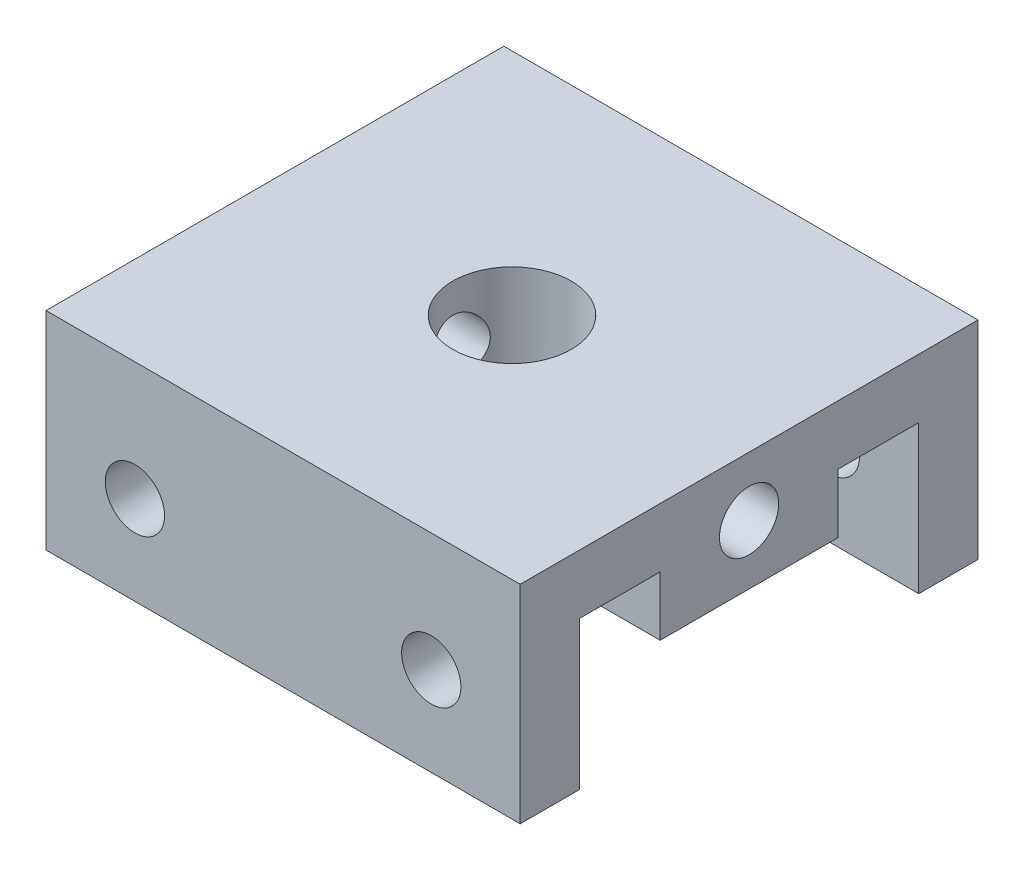
SolidWorks part; units mm, degrees
material "6061-T6 (SS)"
ref_plane "Front Plane" through (0, 0, 0) normal (0, 0, 1) x (1, 0, 0)
ref_plane "Top Plane" through (0, 0, 0) normal (0, 1, 0) x (1, 0, 0)
ref_plane "Right Plane" through (0, 0, 0) normal (1, 0, 0) x (0, 0, -1)
sketch "Sketch1" plane through (0, 0, 0) normal (1, 0, 0) x (0, 0, -1)
  line L0 (18.175, -22.225) -> (24.525, -22.225)
  line L1 (-24.525, 0) -> (24.525, 0)
  line L2 (-24.525, 0) -> (-24.525, -22.225)
  line L3 (-24.525, -22.225) -> (-18.175, -22.225)
  line L4 (24.525, 0) -> (24.525, -22.225)
  line L5 (-18.175, -6.35) -> (18.175, -6.35)
  line L6 (-18.175, -6.35) -> (-18.175, -22.225)
  line L8 (18.175, -6.35) -> (18.175, -22.225)
  point P12 (18.175, -22.225)
  point P14 (0, 0)
  dimension "D1" = 6.35
  dimension "D2" = 6.35
  dimension "D3" = 6.35
  dimension "D4" = 49.0499
  dimension "D5" = 22.225
extrude "Boss-Extrude2" add sketch "Sketch1" along normal blind 25.4 and the other way blind 25.4
sketch "Sketch3" plane through (0, 0, 24.525) normal (0, 0, 1) x (1, 0, 0)
  line L0 (-25.4, 0) -> (-25.4, -22.225) construction
  line L1 (25.4, 0) -> (25.4, -22.225) construction
  line L2 (25.4, 0) -> (-25.4, 0) construction
  circle A0 centre (-15.875, -12.7) radius 3.175
  circle A1 centre (15.875, -12.7) radius 3.175
  dimension "D5" = 6.35
  dimension "D6" = 6.35
  dimension "D1" = 9.525
  dimension "D2" = 9.525
  dimension "D4" = 12.7
extrude "Cut-Extrude1" cut sketch "Sketch3" against normal blind 50.8
sketch "Sketch7" plane through (0, -6.35, 0) normal (0, -1, 0) x (1, 0, 0)
  line L0 (-25.4, 18.175) -> (-25.4, -18.175) construction
  line L1 (-25.4, 9.525) -> (0, 9.525)
  line L2 (-25.4, 9.525) -> (-25.4, -9.525)
  line L3 (-25.4, -9.525) -> (-1.6326, -9.525)
  line L4 (25.4, 18.175) -> (25.4, -18.175) construction
  line L6 (25.4, 9.525) -> (0, 9.525)
  line L7 (25.4, 9.525) -> (25.4, -9.525)
  line L8 (25.4, -9.525) -> (-1.6326, -9.525)
  point P4 (-25.4, 0)
  point P14 (25.4, 0)
  dimension "D2" = 19.05
extrude "Boss-Extrude3" add sketch "Sketch7" along normal blind 6.35
sketch "Sketch4" plane through (0, 0, 0) normal (0, 1, 0) x (1, 0, 0)
  line L3 (-25.4, -9.525) -> (-25.4, 9.525) construction
  line L4 (-25.4, -24.525) -> (25.4, -24.525) construction
  line L5 (-25.4, 24.525) -> (25.4, 24.525) construction
  circle A0 centre (0, 0) radius 6.35
  dimension "D3" = 12.7
  dimension "D1" = 25.4
  dimension "D2" = 24.525
  dimension "D4" = 24.525
extrude "Cut-Extrude2" cut sketch "Sketch4" against normal blind 50.8
sketch "Sketch6" plane through (0, -6.35, 0) normal (0, -1, 0) x (1, 0, 0)
  line L0 (7.1438, 4.1244) -> (7.1438, -4.1244) construction
  line L1 (7.1438, -4.1244) -> (0, -8.2489) construction
  line L2 (0, -8.2489) -> (-7.1438, -4.1244) construction
  line L3 (-7.1438, -4.1244) -> (-7.1438, 4.1244) construction
  line L4 (-7.1438, 4.1244) -> (0, 8.2489) construction
  line L5 (0, 8.2489) -> (7.1438, 4.1244) construction
  circle A0 centre (0, 0) radius 7.1438 construction
  dimension "D1" = 14.2875
sketch "Sketch8" plane through (-25.4, 0, 0) normal (-1, 0, 0) x (0, 0, 1)
  line L2 (9.525, -12.7) -> (-9.525, -12.7) construction
  circle A0 centre (0, -6.35) radius 3.175
  circle A1 centre (0, -6.35) radius 4.7625 construction
  dimension "D1" = 6.35
  dimension "D2" = 9.525
  dimension "D3" = 6.35
extrude "Cut-Extrude3" cut sketch "Sketch8" against normal through all
